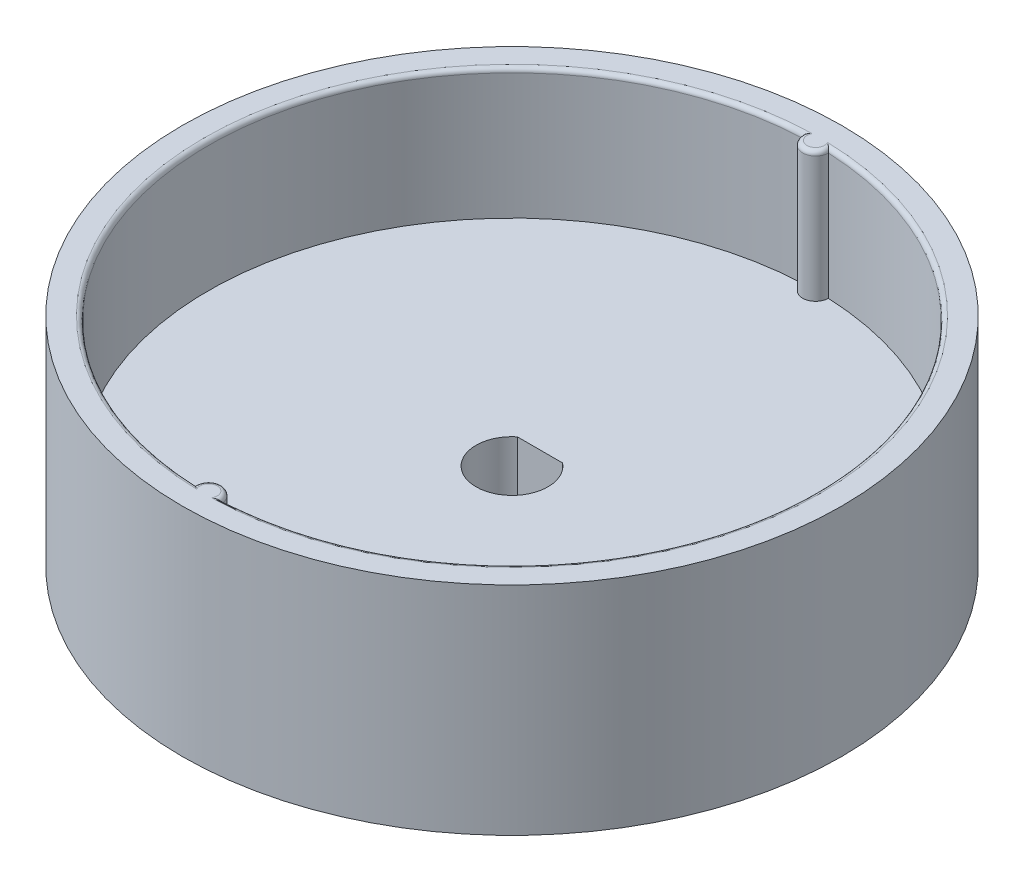
SolidWorks part; units mm, degrees
ref_plane "Front Plane" through (0, 0, 0) normal (0, 0, 1) x (1, 0, 0)
ref_plane "Top Plane" through (0, 0, 0) normal (0, 1, 0) x (1, 0, 0)
ref_plane "Right Plane" through (0, 0, 0) normal (1, 0, 0) x (0, 0, -1)
sketch "Sketch1" plane through (0, 0, 0) normal (0, 1, 0) x (1, 0, 0)
  line L3 (0, 0) -> (0, 3.226) construction
  line L4 (0, 3.226) -> (2.6106, 3.226)
  line L5 (0, 3.226) -> (-2.6106, 3.226)
  arc A0 (1.4997, -34.9679) -> (34.9678, -1.5001) centre (0, 0) ccw
  circle A1 centre (0, 0) radius 38
  arc A2 (-2.6106, 3.226) -> (2.6106, 3.226) centre (0, 0) ccw
  circle A3 centre (0, 0) radius 35 construction
  arc A7 (-1.4997, 34.9679) -> (1.4997, 34.9679) centre (0, 35) ccw
  arc A8 (34.9678, -1.5001) -> (1.4997, 34.9679) centre (0, 0) ccw
  arc A9 (-1.4997, 34.9679) -> (-35, 0) centre (0, 0) ccw
  arc A10 (-35, 0) -> (-1.5003, -34.9678) centre (0, 0) ccw
  arc A11 (1.4997, -34.9679) -> (-1.5003, -34.9678) centre (-0.0003, -34.9679) ccw
  point P8 (-0.0003, -33.4679)
  dimension "D1" = 3
  dimension "D2" = 1.5
  dimension "D3" = 4.15
  dimension "D4" = 35
  dimension "D5" = 1.5
  dimension "D6" = 1.5
  dimension "D11" = 1.4997
extrude "Boss-Extrude1" add sketch "Sketch1" along normal blind 10 contours A10 A0 A8 A7 A9 A2 L5 L4 region at (-0.0003, 0, 32.4784)
extrude "Boss-Extrude2" add sketch "Sketch1<3>" along normal blind 25 contours A1 A10 A9 A7 A8 A0 region at (-36.9252, 0, 0)
sketch "Sketch1<3>" plane through (0, 0, 0) normal (0, 1, 0) x (1, 0, 0) same geometry as "Sketch1"
fillet "Fillet2" radius 0.5 4 edges at (35, 25, 0) (-35, 25, -0.0003) (0, 25, -33.5) (-0.0003, 25, 33.4679)
chamfer "Chamfer1" distance 1 angle 45 2 edges at (0, 0, -3.226) (0, 0, 4.15)
